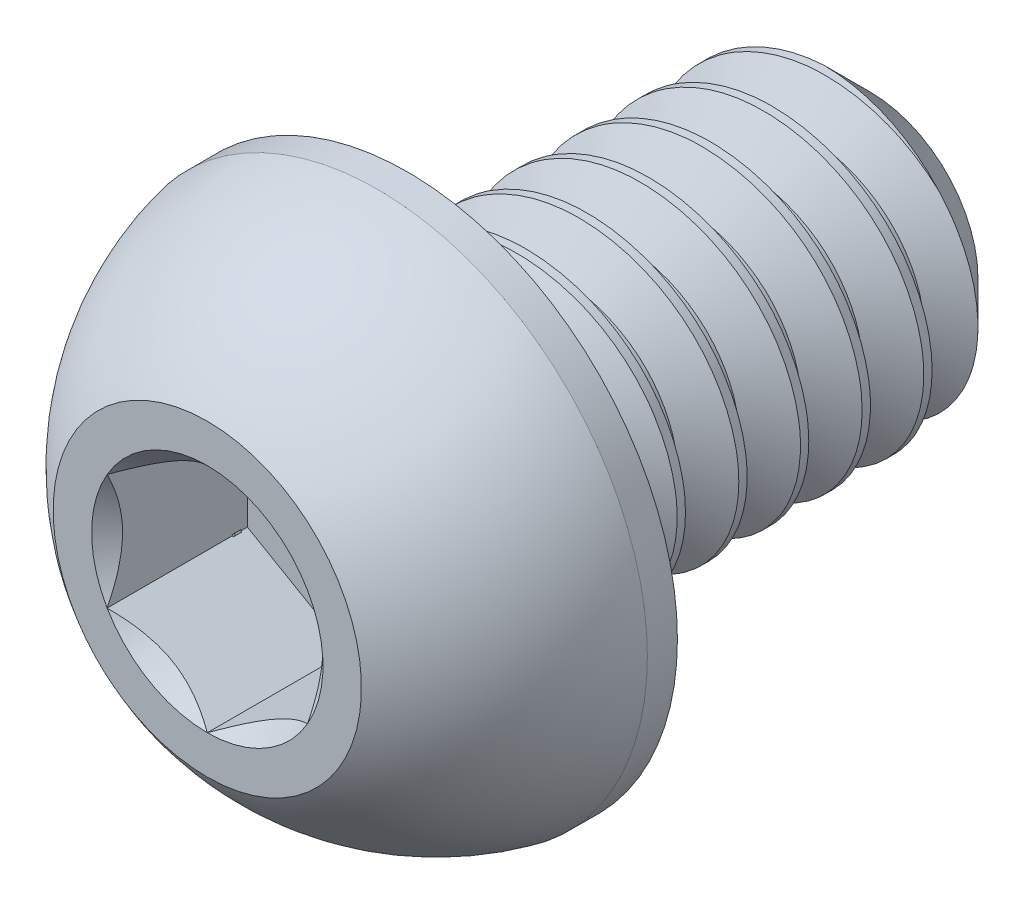
SolidWorks part; units mm, degrees
material "18-8 Stainless Steel"
ref_plane "Front" through (0, 0, 0) normal (0, 0, 1) x (1, 0, 0)
ref_plane "Top" through (0, 0, 0) normal (0, 1, 0) x (1, 0, 0)
ref_plane "Right" through (0, 0, 0) normal (1, 0, 0) x (0, 0, -1)
sketch "Sketch1" plane through (0, 0, 0) normal (1, 0, 0) x (0, 0, -1)
  line L2 (1.3, 1) -> (4.3, 1)
  line L3 (4.3, 1) -> (4.3, 0)
  line L4 (4.3, 0) -> (1.3, 0)
  line L6 (1.105, 1.75) -> (1.3, 1.75) construction
  line L7 (4.3, 1) -> (4.3, -1) construction
  line L8 (0, 0) -> (1.3, 0) construction
  line L9 (1.3, 1.75) -> (1.3, -1.75) construction
  line L11 (1.3, 1) -> (1.3, 0)
  line L13 (0, 0.65) -> (0, -0.65) construction
  line L14 (0, 0.65) -> (0, 1) construction
  arc A3 (0, 1) -> (1.105, 1.75) centre (1.4858, 0) cw construction
  dimension "D1" = 0.195
revolve "Revolve1" add sketch "Sketch1" angle 360 mid plane about L4
sketch "Sketch3" plane through (0, 0, -4.3) normal (0, 0, -1) x (-1, 0, 0)
  circle A0 centre (0, 0) radius 1
curve "Helix/Spiral1" pitch 0.4 height 3.4 radius 1 centre (0, 0, -4.3) axis (0, 0, 1) start towards (0, 1, 0)
chamfer "Chamfer1" distance 0.3 angle 45 1 edges at (0, 1, -4.3)
sketch "Sketch7" plane through (0, 0, 0) normal (1, 0, 0) x (0, 0, -1)
  line L6 (1.105, 1.75) -> (1.3, 1.75) construction
  line L8 (0, 0) -> (1.3, 0) construction
  line L11 (1.3, 1.75) -> (1.3, -1.75) construction
  line L12 (1.105, 1.75) -> (1.3, 1.75)
  line L13 (0, 0) -> (1.3, 0)
  line L14 (0, 0.65) -> (0, -0.65) construction
  line L15 (1.3, 1.75) -> (1.3, 0)
  line L16 (0, 1) -> (0, 0)
  arc A2 (1.105, 1.75) -> (0, 1) centre (1.4858, 0) ccw construction
  arc A3 (1.105, 1.75) -> (0, 1) centre (1.4858, 0) ccw
revolve "Revolve2" add sketch "Sketch7" angle 360 mid plane about L13
sketch "Sketch5" plane through (0, 0, 0) normal (0, 0, 1) x (1, 0, 0)
  line L1 (0.65, -0.3753) -> (0.65, 0.3753)
  line L2 (0.65, 0.3753) -> (0, 0.7506)
  line L3 (0, 0.7506) -> (-0.65, 0.3753)
  line L4 (-0.65, 0.3753) -> (-0.65, -0.3753)
  line L5 (-0.65, -0.3753) -> (0, -0.7506)
  line L6 (0, -0.7506) -> (0.65, -0.3753)
  circle A0 centre (0, 0) radius 0.65 construction
extrude "Cut-Extrude2" cut sketch "Sketch5" against normal blind 0.91
sketch "Sketch6" plane through (0, 0, 0) normal (0, 0, 1) x (1, 0, 0)
  circle A0 centre (0, 0) radius 0.7506
extrude "Cut-Extrude3" cut sketch "Sketch6" against normal blind 0.91 draft 45
sketch "Sketch2" plane through (0, 0, 0) normal (1, 0, 0) x (0, 0, -1)
  line L0 (4, 1) -> (4.346, 1)
  line L1 (4.346, 1) -> (4.2, 0.7471)
  line L2 (4.2, 0.7471) -> (4.146, 0.7471)
  line L3 (4.146, 0.7471) -> (4, 1)
  line L4 (4.073, 0.8736) -> (4.273, 0.8736) construction
  dimension "D1" = 60
  dimension "D2" = 0.054
  dimension "D3" = 0.2
sweep "Cut-Sweep1" cut profiles "Sketch2" path "Helix/Spiral1"
ref_axis "Center Axis 1" through (0, 0, -4.5681) along (0, 0, 1)
ref_plane "Contact Plane 1" through (0, 0, -1.3) normal (0, 0, -1) x (-1, 0, 0)
ref_plane "Contact Plane 2" through (0, 0, 0) normal (0, 0, 1) x (1, 0, 0)
equation "\"D3@Helix/Spiral1\" = \"Lg@Sketch1\" + \"D4@Helix/Spiral1\""
equation "\"D2@Sketch2\"=\"D4@Helix/Spiral1\" * .135"
equation "\"D3@Sketch2\" = \"D4@Helix/Spiral1\" * .5"
equation "\"D1@Chamfer1\" = \"D4@Helix/Spiral1\" * .75"
equation "\"D1@Cut-Extrude2\" = \"Head Ht@Sketch1\" * .7"
equation "\"D1@Sketch1\" = \"Head Ht@Sketch1\" * .15"
equation "\"D1@Cut-Extrude3\" = \"D1@Cut-Extrude2\""
